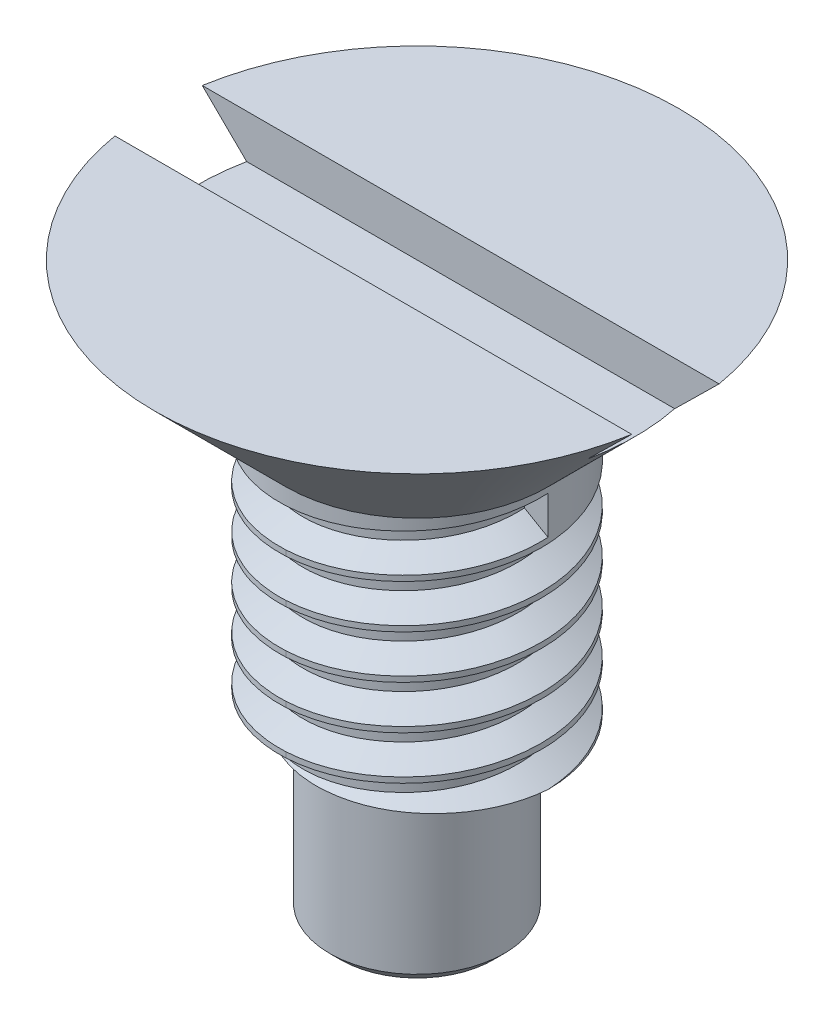
SolidWorks part; units mm, degrees
material "Gray Cast Iron"
ref_plane "Front Plane" through (0, 0, 0) normal (0, 0, 1) x (1, 0, 0)
ref_plane "Top Plane" through (0, 0, 0) normal (0, 1, 0) x (1, 0, 0)
ref_plane "Right Plane" through (0, 0, 0) normal (1, 0, 0) x (0, 0, -1)
sketch "Sketch1" plane through (0, 0, 0) normal (0, 0, 1) x (1, 0, 0)
  line L0 (0, 0) -> (0, -60551.8722) construction
  line L1 (0, 0) -> (60551.8722, 0) construction
  line L2 (0, 0) -> (0, 13)
  line L3 (0, 13) -> (6, 13)
  line L4 (6, 13) -> (3, 10)
  line L5 (3, 10) -> (3, 4)
  line L6 (3, 4) -> (2, 4)
  line L7 (2, 4) -> (2, 0)
  line L8 (2, 0) -> (0, 0)
  dimension "D1" = 4
  dimension "D2" = 4
  dimension "D3" = 6
  dimension "D4" = 13
  dimension "D5" = 45
  dimension "D6" = 3
revolve "Revolve1" add sketch "Sketch1" angle 360 about L0
sketch "Sketch2" plane through (0, 13, 0) normal (0, 1, 0) x (1, 0, 0)
  line L1 (-6, 1) -> (6, 1)
  line L2 (-6, 1) -> (-6, -1)
  line L3 (-6, -1) -> (6, -1)
  line L4 (6, 1) -> (6, -1)
  line L5 (-6, 1) -> (6, -1) construction
  line L6 (-6, -1) -> (6, 1) construction
  circle A0 centre (0, 0) radius 6 construction
  point P0 (0, 0)
  dimension "D1" = 2
extrude "Cut-Extrude1" cut sketch "Sketch2" against normal blind 1
thread "Thread1" pitch 1 method cut profile "Thread Profile1" start angle 0, offset 2, length 7, pitch 1, diameter 6
ref_plane "Plane1" through (3, 2, 0) normal (0, 0, 1) x (1, 0, 0)
sketch "Thread Profile1" plane through (3, 2, 0) normal (0, 0, 1) x (1, 0, 0)
  line L0 (0, 0) -> (0, 1) construction
  line L11 (0, 0) -> (0, 0.875)
  line L12 (0, 0.875) -> (-0.5413, 0.5625)
  line L13 (-0.5413, 0.5625) -> (-0.5413, 0.3125)
  line L15 (-0.5413, 0.3125) -> (0, 0)
  line L17 (-0.5413, 0.4375) -> (0, 0.4375) construction
  point P2 (0, 0)
  dimension "Pitch" = 1
  dimension "Profile_Angle" = 60
  dimension "Profile_Land" = 0.25
  dimension "Profile_Height" = 0.5413
chamfer "Chamfer1" distance 0.25 angle 45 1 edges at (0, 0, 2)
